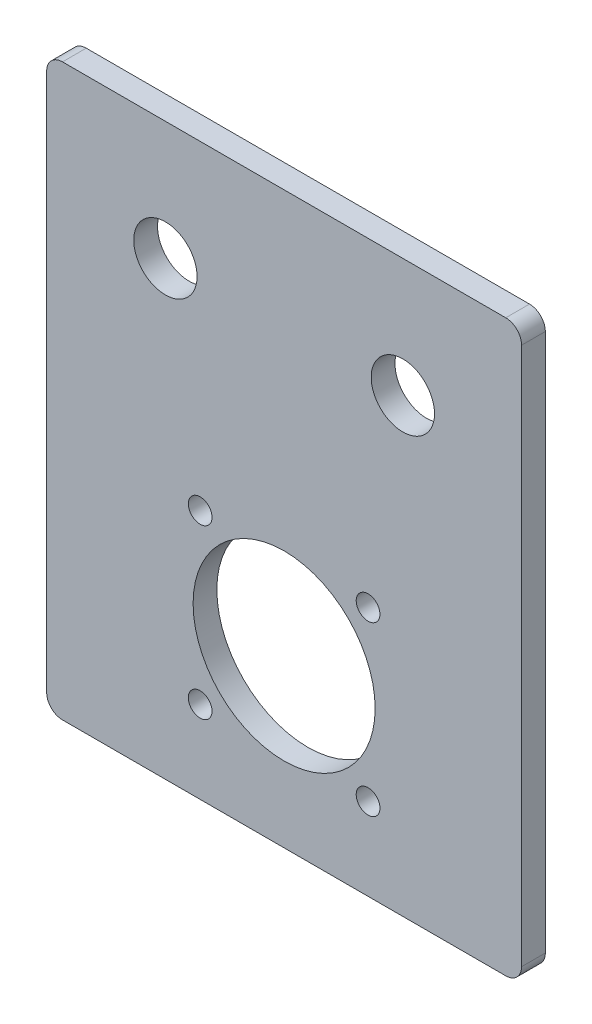
SolidWorks part; units mm, degrees
ref_plane "前视基准面" through (0, 0, 0) normal (0, 0, 1) x (1, 0, 0)
ref_plane "上视基准面" through (0, 0, 0) normal (0, 1, 0) x (1, 0, 0)
ref_plane "右视基准面" through (0, 0, 0) normal (1, 0, 0) x (0, 0, -1)
sketch "草图1" plane through (0, 0, 0) normal (0, 0, 1) x (1, 0, 0)
  line L1 (0, 0) -> (60, 0)
  line L2 (0, 0) -> (0, 72)
  line L3 (0, 72) -> (60, 72)
  line L4 (60, 0) -> (60, 72)
  dimension "D1" = 60
  dimension "D2" = 72
extrude "凸台-拉伸1" add sketch "草图1" along normal blind 3
sketch "草图2" plane through (0, 0, 3) normal (0, 0, 1) x (1, 0, 0)
  line L0 (0, 72) -> (0, 0) construction
  line L1 (0, 0) -> (60, 0) construction
  line L2 (60, 72) -> (0, 72) construction
  line L3 (60, 0) -> (60, 72) construction
  circle A0 centre (30, 21) radius 11.5
  circle A1 centre (19.3934, 31.6066) radius 1.5
  circle A2 centre (40.6066, 31.6066) radius 1.5
  circle A3 centre (40.6066, 10.3934) radius 1.5
  circle A4 centre (19.3934, 10.3934) radius 1.5
  circle A5 centre (15, 57) radius 4
  circle A6 centre (45, 57) radius 4
  point P16 (30, 21)
  point P25 (51.0586, 72)
  point P26 (63.0587, 57.6039)
  dimension "D9" = 8
  dimension "D10" = 8
  dimension "D11" = 3
  dimension "D12" = 23
  dimension "D1" = 30
  dimension "D2" = 21
  dimension "D3" = 15
  dimension "D5" = 15
  dimension "D6" = 15
  dimension "D7" = 15
  dimension "D8" = 15
  dimension "D4" = 4
extrude "切除-拉伸1" cut sketch "草图2" against normal through all
fillet "圆角1" radius 2 4 edges at (0, 72, 1.5) (60, 72, 1.5) (60, 0, 1.5) (0, 0, 1.5)
